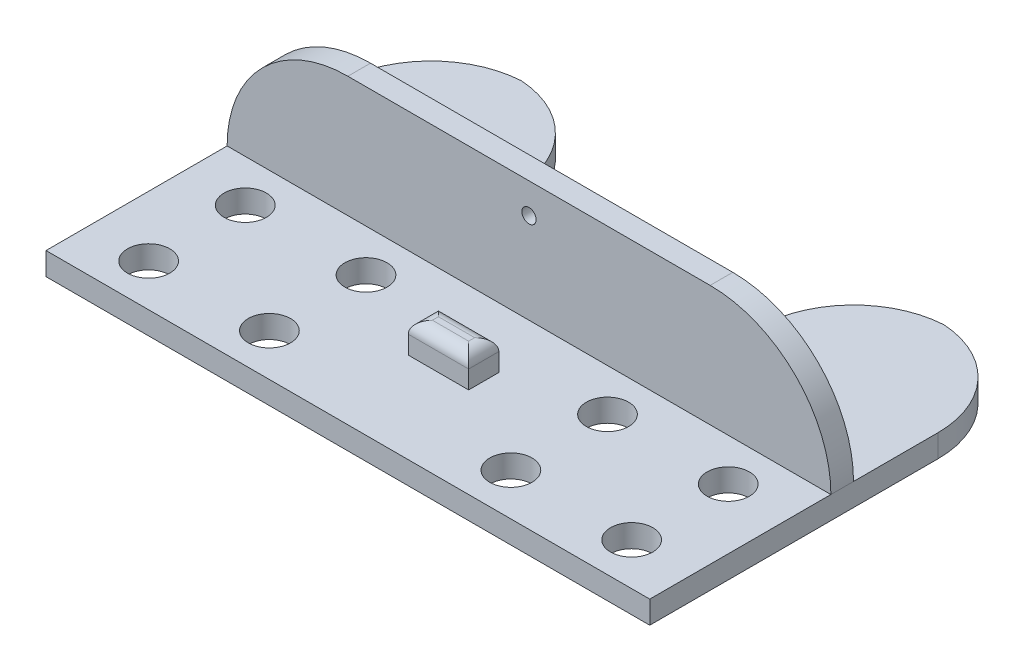
SolidWorks part; units mm, degrees
ref_plane "Front Plane" through (0, 0, 0) normal (0, 0, 1) x (1, 0, 0)
ref_plane "Top Plane" through (0, 0, 0) normal (0, 1, 0) x (1, 0, 0)
ref_plane "Right Plane" through (0, 0, 0) normal (1, 0, 0) x (0, 0, -1)
sketch "Sketch1" plane through (0, 0, 0) normal (1, 0, 0) x (0, 0, -1)
  line L0 (0, 0) -> (-42.8625, 0)
  line L1 (-42.8625, 0) -> (-42.8625, 4.7625)
  line L2 (-42.8625, 4.7625) -> (-4.7625, 4.7625)
  line L3 (-4.7625, 4.7625) -> (-4.7625, 30.1625)
  line L4 (-4.7625, 30.1625) -> (0, 30.1625)
  line L5 (0, 30.1625) -> (0, 0)
  line L7 (0, 0) -> (38.1, 0)
  line L8 (0, 0) -> (0, 4.7625)
  line L9 (0, 4.7625) -> (38.1, 4.7625)
  line L10 (38.1, 0) -> (38.1, 4.7625)
  dimension "D1" = 38.1
  dimension "D2" = 25.4
  dimension "D3" = 4.7625
  dimension "D4" = 38.1
extrude "Boss-Extrude1" add sketch "Sketch1" along normal blind 127 contours L5 L4 L3 L2 L1 L0 | L7 L10 L9 L5 region at (0, 0.5241, 21.4313) region at (0, 2.3813, -19.05)
sketch "Sketch2" plane through (0, 4.7625, 0) normal (0, 1, 0) x (1, 0, 0)
  line L0 (127, -42.8625) -> (0, -42.8625) construction
  line L1 (57.15, -23.8125) -> (69.85, -23.8125)
  line L2 (57.15, -23.8125) -> (57.15, -17.4625)
  line L3 (57.15, -17.4625) -> (69.85, -17.4625)
  line L4 (69.85, -23.8125) -> (69.85, -17.4625)
  line L7 (127, -4.7625) -> (0, -4.7625) construction
  point P4 (63.5, -23.8125)
  point P7 (63.5, -42.8625)
  dimension "D1" = 6.35
  dimension "D2" = 12.7
  dimension "D3" = 12.7
extrude "Boss-Extrude2" add sketch "Sketch2" along normal blind 6.35
sketch "Sketch3" plane through (0, 0, 4.7625) normal (0, 0, 1) x (1, 0, 0)
  line L0 (127, 30.1625) -> (0, 30.1625) construction
  line L1 (127, 4.7625) -> (0, 4.7625) construction
  circle A0 centre (63.5, 23.8125) radius 1.5
  point P5 (63.5, 30.1625)
  dimension "D1" = 3
  dimension "D2" = 19.05
extrude "Cut-Extrude1" cut sketch "Sketch3" against normal through all
fillet "Fillet1" radius 2.54 4 edges at (63.5, 11.1125, 17.4625) (69.85, 11.1125, 20.6375) (63.5, 11.1125, 23.8125) (57.15, 11.1125, 20.6375)
sketch "Sketch4" plane through (0, 4.7625, 0) normal (0, 1, 0) x (1, 0, 0)
  line L0 (127, 38.1) -> (0, 38.1) construction
  line L1 (38.1, 38.1) -> (88.9, 38.1)
  line L2 (38.1, 38.1) -> (38.1, 0)
  line L3 (38.1, 0) -> (88.9, 0)
  line L4 (88.9, 38.1) -> (88.9, 0)
  line L5 (127, 0) -> (0, 0) construction
  point P8 (-19.3946, 38.1)
  point P9 (-56.1353, 38.1)
  point P10 (63.5, 38.1)
  point P11 (63.5, 38.1)
  point P12 (42.3707, 0)
  dimension "D1" = 50.8
extrude "Cut-Extrude2" cut sketch "Sketch4" against normal through all
fillet "Fillet2" radius 20.32 4 edges at (0, 2.3813, -38.1) (38.1, 2.3812, -38.1) (88.9, 2.3812, -38.1) (127, 2.3813, -38.1)
sketch "Sketch5" plane through (0, 4.7625, 0) normal (0, 1, 0) x (1, 0, 0)
  line L0 (12.7, -13.6525) -> (38.1, -13.6525) construction
  line L1 (38.1, -13.6525) -> (38.1, -33.9725) construction
  line L2 (12.7, -33.9725) -> (38.1, -33.9725) construction
  line L3 (12.7, -13.6525) -> (12.7, -33.9725) construction
  line L4 (88.9, -13.6525) -> (114.3, -13.6525) construction
  line L5 (114.3, -13.6525) -> (114.3, -33.9725) construction
  line L6 (114.3, -33.9725) -> (88.9, -33.9725) construction
  line L7 (88.9, -33.9725) -> (88.9, -13.6525) construction
  line L8 (88.9, -13.6525) -> (38.1, -13.6525) construction
  line L9 (127, -42.8625) -> (0, -42.8625) construction
  line L11 (0, -42.8625) -> (0, -4.7625) construction
  circle A0 centre (12.7, -13.6525) radius 4.445
  circle A1 centre (12.7, -33.9725) radius 4.445
  circle A2 centre (114.3, -13.6525) radius 4.445
  circle A3 centre (114.3, -33.9725) radius 4.445
  circle A4 centre (38.1, -13.6525) radius 4.445
  circle A5 centre (88.9, -13.6525) radius 4.445
  circle A6 centre (38.1, -33.9725) radius 4.445
  circle A7 centre (88.9, -33.9725) radius 4.445
  point P8 (63.5, -13.6525)
  point P11 (63.5, -42.8625)
  point P12 (39.7808, -12.1103)
  point P13 (14.1067, -11.589)
  point P14 (12.7, -23.8125)
  point P17 (37.5653, -30.6165)
  point P20 (11.7609, -13.6743)
  point P27 (0, -23.8125)
  dimension "D1" = 8.89
  dimension "D2" = 8.89
  dimension "D3" = 12.7
  dimension "D4" = 25.4
extrude "Cut-Extrude3" cut sketch "Sketch5" against normal through all
fillet "Fillet3" radius 25.4 2 edges at (127, 30.1625, 2.3813) (0, 30.1625, 2.3813)
